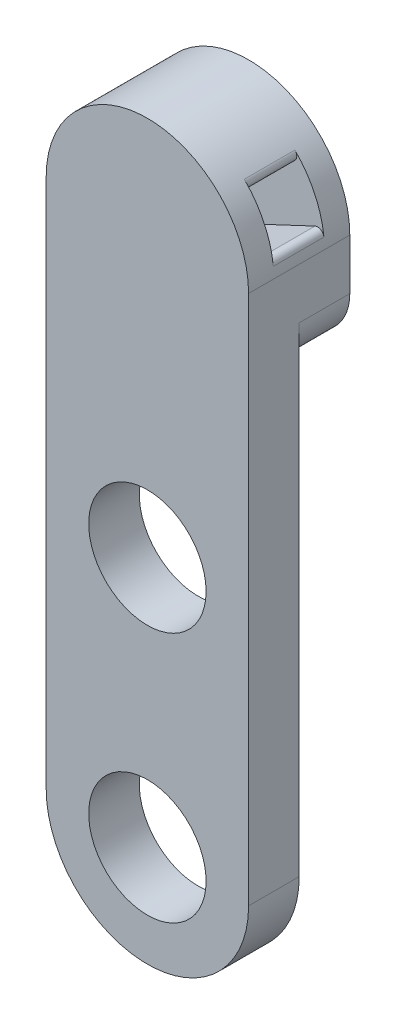
SolidWorks part; units mm, degrees
material "ABS"
ref_plane "Front Plane" through (0, 0, 0) normal (0, 0, 1) x (1, 0, 0)
ref_plane "Top Plane" through (0, 0, 0) normal (0, 1, 0) x (1, 0, 0)
ref_plane "Right Plane" through (0, 0, 0) normal (1, 0, 0) x (0, 0, -1)
sketch "Sketch1" plane through (0, 0, 0) normal (0, 0, 1) x (1, 0, 0)
  line L2 (0, 5.5562) -> (0, -5.5562) construction
  line L6 (0, 5.5562) -> (0, -12.7) construction
  line L9 (17.4625, 13.4938) -> (11.1125, 13.4938)
  line L10 (11.1125, 13.4938) -> (11.1125, 5.5563)
  line L11 (17.4625, 13.4938) -> (17.4625, -5.5562)
  line L12 (17.4625, -5.5562) -> (0, -5.5562)
  line L13 (11.1125, 5.5563) -> (11.1125, -5.5563) construction
  line L14 (14.2875, 13.4938) -> (14.2875, -5.5563) construction
  line L15 (14.2875, 7.9058) -> (14.2875, 0.0318)
  line L16 (0, 5.5562) -> (11.1125, 5.5563)
  line L17 (15.875, -5.5563) -> (15.875, -5.1309)
  line L18 (12.7, -5.5563) -> (15.875, -5.5563)
  line L19 (12.7, -5.5563) -> (12.7, -6.3691)
  line L20 (12.7, -6.3691) -> (15.875, -6.3691)
  line L21 (15.875, -5.5563) -> (15.875, -6.3691)
  circle A0 centre (0, 0) radius 5.5562 construction
  arc A2 (0, 5.5562) -> (0, -5.5562) centre (0, 0) ccw
  circle A4 centre (0, 0) radius 1.7859
  circle A16 centre (14.2875, 7.9058) radius 1.5875
  circle A20 centre (14.2875, 0.0318) radius 1.5875
  circle A22 centre (0, 0) radius 12.7 construction
  circle A25 centre (0, 0) radius 9.1281 construction
  circle A29 centre (14.2875, 10.3188) radius 3.175
  circle A30 centre (14.2875, -2.3813) radius 3.175
  circle A32 centre (0, -9.1281) radius 3.5719
  circle A33 centre (0, -9.1281) radius 1.7859
  circle A34 centre (-6.5741, -6.3327) radius 3.5719
  circle A35 centre (7.1437, -9.1281) radius 3.5719
  point P17 (14.2875, -5.5563)
  point P20 (14.2875, 3.9688)
  dimension "D1" = 7.874
  dimension "D2" = 11.1125
  dimension "D3" = 3.5719
  dimension "D5" = 6.35
  dimension "D6" = 7.1437
  dimension "D8" = 3.175
  dimension "D9" = 0.8128
  dimension "D11" = 3.5719
  dimension "D4" = 19.05
  dimension "D10" = 3.175
sketch "Sketch2" plane through (0, 0, 0) normal (0, 0, 1) x (1, 0, 0)
  circle A0 centre (0, 0) radius 5.5562
  circle A1 centre (0, -9.1281) radius 3.5719
  circle A2 centre (-6.5741, -6.3327) radius 3.5719
  circle A3 centre (6.5741, -6.3327) radius 3.5719
  circle A4 centre (0, 0) radius 9.1281 construction
  circle A5 centre (0, 0) radius 2.0399
  circle A6 centre (0, -9.1281) radius 1.5319
  dimension "D1" = 4.0799
  dimension "D2" = 3.0639
sketch "Sketch3" plane through (0, 0, 0) normal (0, 0, 1) x (1, 0, 0)
  line L0 (17.4625, 0.0318) -> (17.4625, 13.4938)
  line L1 (17.4625, 13.4938) -> (11.1125, 13.4938) construction
  line L2 (11.1125, 13.4938) -> (11.1125, 0.0318)
  line L3 (17.4625, 13.4938) -> (11.1125, 13.4938) construction
  line L4 (11.1125, 16.6688) -> (11.1125, 13.4938)
  line L5 (17.4625, 16.6688) -> (17.4625, 13.4938)
  circle A0 centre (14.2875, 0.0318) radius 1.8415
  circle A1 centre (14.2875, 7.9058) radius 1.8415
  circle A2 centre (14.2875, 10.3188) radius 3.175
  circle A3 centre (14.2875, 0.0318) radius 3.175
  circle A4 centre (14.2875, 16.6688) radius 3.175
  dimension "D1" = 3.683
extrude "Boss-Extrude1" add sketch "Sketch3" along normal blind 1.5875 contours L0 L1 L2 A3 A1 | L1 A4 L4 | A4 | L1 L5 A4 | A3 A0 | A2 A1 | A2 L1 L2 | L0 L1 A2 region at (14.2875, 5.0019, 0) region at (14.2875, -3.0534, 0) region at (16.7533, 12.7846, 0) region at (14.2875, 10.915, 0) region at (16.7533, 14.2029, 0) region at (11.8217, 12.7846, 0) region at (11.8217, 14.2029, 0) region at (14.2875, 16.6688, 0)
extrude "Boss-Extrude2" add sketch "Sketch3<3>" against normal blind 1.5875 contours L1 L5 A4 | L1 A4 L4 | A4 | A2 L1 L2 | L0 L1 A2 region at (16.7533, 12.7846, 0) region at (16.7533, 14.2029, 0) region at (11.8217, 12.7846, 0) region at (11.8217, 14.2029, 0) region at (14.2875, 16.6688, 0)
sketch "Sketch3<3>" plane through (0, 0, 0) normal (0, 0, 1) x (1, 0, 0) same geometry as "Sketch3"
sketch "Sketch4" plane through (0, 0, -1.5875) normal (0, 0, -1) x (-1, 0, 0)
  line L6 (-17.2085, 16.6688) -> (-17.2085, 12.1148)
  line L7 (-11.3665, 12.1148) -> (-11.3665, 16.6688)
  line L8 (-17.2085, 16.6688) -> (-17.2085, 12.1148)
  line L9 (-11.3665, 12.1148) -> (-11.3665, 16.6688)
  line L10 (-17.4625, 16.6688) -> (-17.4625, 10.3188)
  line L11 (-11.1125, 10.3188) -> (-11.1125, 16.6688)
  line L12 (-17.4625, 16.6688) -> (-17.4625, 10.3188)
  line L13 (-11.1125, 10.3188) -> (-11.1125, 16.6688)
  circle A4 centre (-14.2875, 10.3188) radius 3.429
  arc A6 (-11.3665, 16.6688) -> (-17.2085, 16.6688) centre (-14.2875, 16.6688) ccw
  arc A7 (-11.3665, 12.1148) -> (-17.2085, 12.1148) centre (-14.2875, 10.3188) ccw
  arc A8 (-11.3665, 16.6688) -> (-17.2085, 16.6688) centre (-14.2875, 16.6688) ccw
  arc A9 (-11.3665, 12.1148) -> (-17.2085, 12.1148) centre (-14.2875, 10.3188) ccw
  arc A10 (-11.1125, 16.6688) -> (-17.4625, 16.6688) centre (-14.2875, 16.6688) ccw
  arc A11 (-11.1125, 10.3188) -> (-17.4625, 10.3188) centre (-14.2875, 10.3188) ccw
  arc A12 (-11.1125, 16.6688) -> (-17.4625, 16.6688) centre (-14.2875, 16.6688) ccw
  arc A13 (-11.1125, 10.3188) -> (-17.4625, 10.3188) centre (-14.2875, 10.3188) ccw
  arc M12 (-17.4625, 10.3188) -> (-11.1125, 10.3188) centre (-14.2875, 10.3188) cw
  line M13 (-11.1125, 10.3188) -> (-11.1125, 16.6688)
  dimension "D1" = 0.254
  dimension "D2" = 0
extrude "Cut-Extrude1" cut sketch "Sketch4" against normal blind 1.5875 contours A4 L12 M13 M12 region at (14.2875, 13.6756, -1.5875)
sketch "Sketch5" plane through (0, 0, -1.5875) normal (0, 0, -1) x (-1, 0, 0)
  line L0 (-17.4625, 15.1872) -> (-11.1125, 15.1872) construction
  line L2 (-17.4625, 16.6688) -> (-17.4625, 11.6139) construction
  line L3 (-11.1125, 16.6688) -> (-11.1125, 11.6139) construction
  line L4 (-11.1125, 15.1872) -> (-19.7689, 19.265) construction
  arc A0 (-11.1125, 16.6688) -> (-17.4625, 16.6688) centre (-14.2875, 16.6688) ccw construction
  point P13 (-14.2875, 19.8438)
  dimension "D1" = 4.6566
  dimension "D2" = 25.224
sketch "Sketch8" plane through (11.1125, 0, 0) normal (-1, 0, 0) x (0, 0, 1)
  line L0 (-1.5875, 15.1872) -> (1.5875, 15.1872) construction
  line L1 (1.5875, 16.6687) -> (1.5875, 0.0317) construction
ref_plane "Plane3" through (-3.8369, 8.1449, 0) normal (-0.4262, 0.9046, 0) x (0.9046, 0.4262, 0)
ref_plane "Plane4" through (14.9493, 7.0423, 0) normal (-0.9046, -0.4262, 0) x (0, 0, 1)
sketch "Sketch9" plane through (14.9493, 7.0423, 0) normal (-0.9046, -0.4262, 0) x (0, 0, 1)
  line L0 (-1.5875, 9.0034) -> (1.5875, 9.0034) construction
  line L2 (-0.7937, 8.2096) -> (0.7937, 8.2096)
  line L3 (-0.7937, 8.2096) -> (-0.7937, 9.7971)
  line L4 (-0.7937, 9.7971) -> (0.7937, 9.7971)
  line L5 (0.7937, 8.2096) -> (0.7937, 9.7971)
  line L6 (-0.7937, 8.2096) -> (0.7937, 9.7971) construction
  line L7 (-0.7937, 9.7971) -> (0.7937, 8.2096) construction
  circle A0 centre (0, 9.0034) radius 0.7937 construction
  point P4 (0, 9.0034)
  dimension "D1" = 1.5875
extrude "Cut-Extrude3" cut sketch "Sketch9" against normal through all both and the other way through all
fillet "Fillet1" radius 1.5875 2 edges at (17.4625, 11.6139, -0.7937) (11.1125, 11.6139, -0.7937)
fillet "Fillet3" radius 0.1985 5 edges at (11.1125, 16.0646, 0) (16.7218, 18.707, 0) (17.4043, 17.2737, 0) (11.1125, 14.3098, 0.3969) (11.2716, 14.3847, -0.3969)
